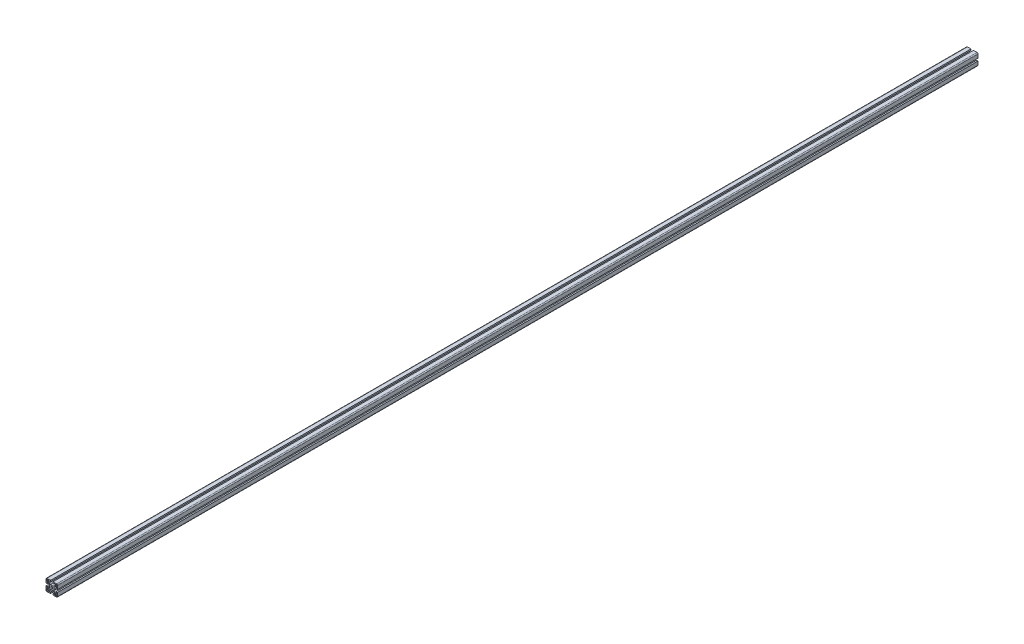
SolidWorks part; units mm, degrees
ref_plane "Front Plane" through (0, 0, 0) normal (0, 0, 1) x (1, 0, 0)
ref_plane "Top Plane" through (0, 0, 0) normal (0, 1, 0) x (1, 0, 0)
ref_plane "Right Plane" through (0, 0, 0) normal (1, 0, 0) x (0, 0, -1)
sketch "Sketch1" plane through (0, 0, 0) normal (0, 0, 1) x (1, 0, 0)
  line L0 (-11.8872, 17.272) -> (-14.478, 17.272)
  line L1 (-11.8872, 11.8872) -> (-11.8872, 17.272)
  line L2 (-17.272, 11.8872) -> (-11.8872, 11.8872)
  line L3 (-17.272, 14.478) -> (-17.272, 11.8872)
  line L4 (14.478, 17.272) -> (11.8872, 17.272)
  line L5 (17.272, 11.8872) -> (17.272, 14.478)
  line L6 (11.8872, 11.8872) -> (17.272, 11.8872)
  line L7 (11.8872, 17.272) -> (11.8872, 11.8872)
  line L8 (11.8872, -17.272) -> (14.478, -17.272)
  line L9 (11.8872, -11.8872) -> (11.8872, -17.272)
  line L10 (17.272, -11.8872) -> (11.8872, -11.8872)
  line L11 (17.272, -14.478) -> (17.272, -11.8872)
  line L12 (-14.478, -17.272) -> (-11.8872, -17.272)
  line L13 (-17.272, -11.8872) -> (-17.272, -14.478)
  line L14 (-11.8872, -11.8872) -> (-17.272, -11.8872)
  line L15 (-11.8872, -17.272) -> (-11.8872, -11.8872)
  line L16 (-6.731, 4.5757) -> (-6.731, -4.5757)
  line L17 (-6.731, -4.5757) -> (-12.4423, -10.287)
  line L18 (-12.4423, -10.287) -> (-15.6718, -10.287)
  line L19 (-15.6718, -10.287) -> (-15.6718, -6.858)
  line L20 (-15.6718, -6.858) -> (-14.478, -6.858)
  line L21 (-14.478, -6.858) -> (-14.478, -4.064)
  line L22 (-14.478, -4.064) -> (-19.05, -4.064)
  line L23 (-19.05, -4.064) -> (-19.05, -15.875)
  line L24 (-15.875, -19.05) -> (-4.064, -19.05)
  line L25 (-4.064, -19.05) -> (-4.064, -14.478)
  line L26 (-4.064, -14.478) -> (-6.858, -14.478)
  line L27 (-6.858, -14.478) -> (-6.858, -15.6718)
  line L28 (-6.858, -15.6718) -> (-10.287, -15.6718)
  line L29 (-10.287, -15.6718) -> (-10.287, -12.4423)
  line L30 (-10.287, -12.4423) -> (-4.5757, -6.731)
  line L31 (-4.5757, -6.731) -> (4.5757, -6.731)
  line L32 (4.5757, -6.731) -> (10.287, -12.4423)
  line L33 (10.287, -12.4423) -> (10.287, -15.6718)
  line L34 (10.287, -15.6718) -> (6.858, -15.6718)
  line L35 (6.858, -15.6718) -> (6.858, -14.478)
  line L36 (6.858, -14.478) -> (4.064, -14.478)
  line L37 (4.064, -14.478) -> (4.064, -19.05)
  line L38 (4.064, -19.05) -> (15.875, -19.05)
  line L39 (19.05, -15.875) -> (19.05, -4.064)
  line L40 (19.05, -4.064) -> (14.478, -4.064)
  line L41 (14.478, -4.064) -> (14.478, -6.858)
  line L42 (14.478, -6.858) -> (15.6718, -6.858)
  line L43 (15.6718, -6.858) -> (15.6718, -10.287)
  line L44 (15.6718, -10.287) -> (12.4423, -10.287)
  line L45 (12.4423, -10.287) -> (6.731, -4.5757)
  line L46 (6.731, -4.5757) -> (6.731, 4.5757)
  line L47 (6.731, 4.5757) -> (12.4423, 10.287)
  line L48 (12.4423, 10.287) -> (15.6718, 10.287)
  line L49 (15.6718, 10.287) -> (15.6718, 6.858)
  line L50 (15.6718, 6.858) -> (14.478, 6.858)
  line L51 (14.478, 6.858) -> (14.478, 4.064)
  line L52 (14.478, 4.064) -> (19.05, 4.064)
  line L53 (19.05, 4.064) -> (19.05, 15.875)
  line L54 (15.875, 19.05) -> (4.064, 19.05)
  line L55 (4.064, 19.05) -> (4.064, 14.478)
  line L56 (4.064, 14.478) -> (6.858, 14.478)
  line L57 (6.858, 14.478) -> (6.858, 15.6718)
  line L58 (6.858, 15.6718) -> (10.287, 15.6718)
  line L59 (10.287, 15.6718) -> (10.287, 12.4423)
  line L60 (10.287, 12.4423) -> (4.5757, 6.731)
  line L61 (4.5757, 6.731) -> (-4.5757, 6.731)
  line L62 (-4.5757, 6.731) -> (-10.287, 12.4423)
  line L63 (-10.287, 12.4423) -> (-10.287, 15.6718)
  line L64 (-10.287, 15.6718) -> (-6.858, 15.6718)
  line L65 (-6.858, 15.6718) -> (-6.858, 14.478)
  line L66 (-6.858, 14.478) -> (-4.064, 14.478)
  line L67 (-4.064, 14.478) -> (-4.064, 19.05)
  line L68 (-4.064, 19.05) -> (-15.875, 19.05)
  line L69 (-19.05, 15.875) -> (-19.05, 4.064)
  line L70 (-19.05, 4.064) -> (-14.478, 4.064)
  line L71 (-14.478, 4.064) -> (-14.478, 6.858)
  line L72 (-14.478, 6.858) -> (-15.6718, 6.858)
  line L73 (-15.6718, 6.858) -> (-15.6718, 10.287)
  line L74 (-15.6718, 10.287) -> (-12.4423, 10.287)
  line L75 (-12.4423, 10.287) -> (-6.731, 4.5757)
  circle A0 centre (0, 0) radius 3.2639
  arc A1 (-19.05, -15.875) -> (-15.875, -19.05) centre (-15.875, -15.875) ccw
  arc A2 (15.875, -19.05) -> (19.05, -15.875) centre (15.875, -15.875) ccw
  arc A3 (19.05, 15.875) -> (15.875, 19.05) centre (15.875, 15.875) ccw
  arc A4 (-15.875, 19.05) -> (-19.05, 15.875) centre (-15.875, 15.875) ccw
  arc A5 (-14.478, 17.272) -> (-17.272, 14.478) centre (-14.478, 14.478) ccw
  arc A6 (17.272, 14.478) -> (14.478, 17.272) centre (14.478, 14.478) ccw
  arc A7 (14.478, -17.272) -> (17.272, -14.478) centre (14.478, -14.478) ccw
  arc A8 (-17.272, -14.478) -> (-14.478, -17.272) centre (-14.478, -14.478) ccw
extrude "Boss-Extrude1" add sketch "Sketch1" along normal mid plane 3048
